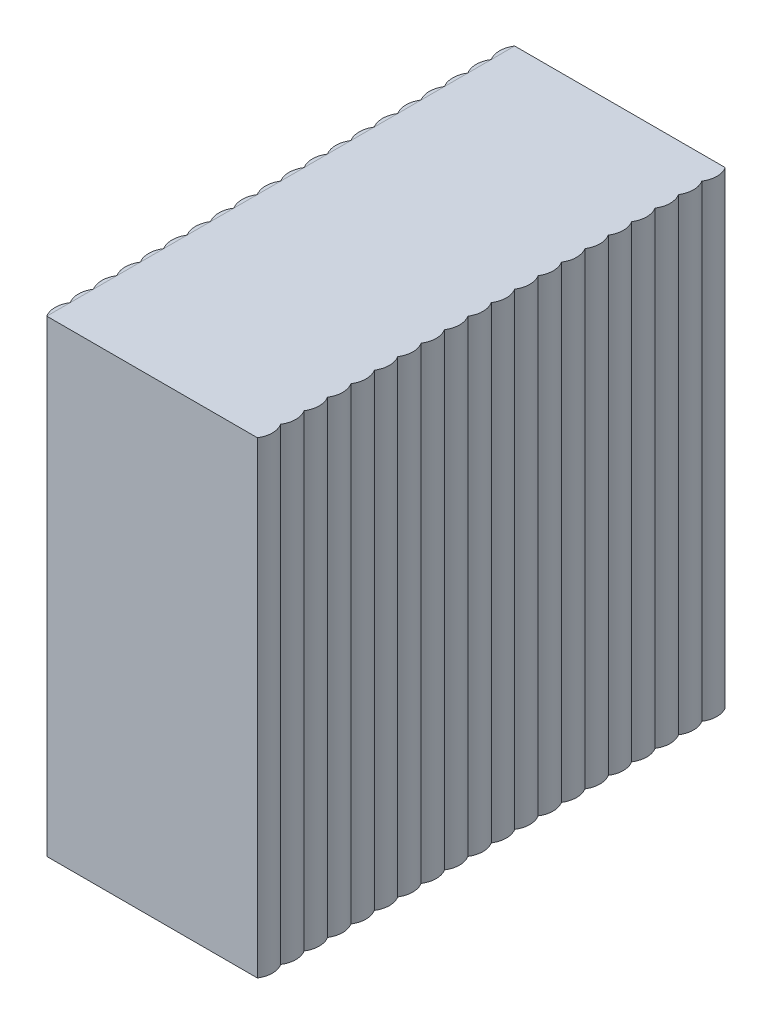
SolidWorks part; units mm, degrees
ref_plane "前视基准面" through (0, 0, 0) normal (0, 0, 1) x (1, 0, 0)
ref_plane "上视基准面" through (0, 0, 0) normal (0, 1, 0) x (1, 0, 0)
ref_plane "右视基准面" through (0, 0, 0) normal (1, 0, 0) x (0, 0, -1)
sketch "草图1" plane through (0, 0, 0) normal (1, 0, 0) x (0, 0, -1)
  line L1 (0, 0) -> (5, 0)
  line L2 (0, 0) -> (0, 5)
  line L3 (0, 5) -> (5, 5)
  line L4 (5, 0) -> (5, 5)
  dimension "D1" = 5
  dimension "D2" = 5
extrude "凸台-拉伸1" add sketch "草图1" along normal blind 2.25
sketch "草图3" plane through (0, 0, 0) normal (0, -1, 0) x (1, 0, 0)
  line L0 (0.1967, -4.875) -> (0.1967, -4.625) construction
  line L2 (-0.0364, -5.0397) -> (-0.0364, -0.0247)
  line L3 (0, -5) -> (0, 0)
  circle A0 centre (0.1967, -4.875) radius 0.2331
  circle A1 centre (0.1967, -4.625) radius 0.2331
  circle A2 centre (0.1967, -4.375) radius 0.2331
  circle A3 centre (0.1967, -4.125) radius 0.2331
  circle A4 centre (0.1967, -3.875) radius 0.2331
  circle A5 centre (0.1967, -3.625) radius 0.2331
  circle A6 centre (0.1967, -3.375) radius 0.2331
  circle A7 centre (0.1967, -3.125) radius 0.2331
  circle A8 centre (0.1967, -2.875) radius 0.2331
  circle A9 centre (0.1967, -2.625) radius 0.2331
  circle A10 centre (0.1967, -2.375) radius 0.2331
  circle A11 centre (0.1967, -2.125) radius 0.2331
  circle A12 centre (0.1967, -1.875) radius 0.2331
  circle A13 centre (0.1967, -1.625) radius 0.2331
  circle A14 centre (0.1967, -1.375) radius 0.2331
  circle A15 centre (0.1967, -1.125) radius 0.2331
  circle A16 centre (0.1967, -0.875) radius 0.2331
  circle A17 centre (0.1967, -0.625) radius 0.2331
  circle A18 centre (0.1967, -0.375) radius 0.2331
  circle A19 centre (0.1967, -0.125) radius 0.2331
  line M21 (0, 0) -> (0, -5)
  dimension "D1" = 20
  dimension "D2" = 0.25
extrude "凸台-拉伸3" add sketch "草图3" against normal up to surface (5 mm away) separate body contours L3 A0 | L3 A1 | L3 A2 | L3 A3 | L3 A4 | L3 A5 | L3 A6 | L3 A7 | L3 A8 | L3 A9 | L3 A10 | L3 A11 | L3 A12 | L3 A13 | L3 A14 | L3 A15 | L3 A16 | L3 A17 | L3 A18 | A19 M21 region at (-0.0146, 0, -4.875) region at (-0.0146, 0, -4.625) region at (-0.0146, 0, -4.375) region at (-0.0146, 0, -4.125) region at (-0.0146, 0, -3.875) region at (-0.0146, 0, -3.625) region at (-0.0146, 0, -3.375) region at (-0.0146, 0, -3.125) region at (-0.0146, 0, -2.875) region at (-0.0146, 0, -2.625) region at (-0.0146, 0, -2.375) region at (-0.0146, 0, -2.125) region at (-0.0146, 0, -1.875) region at (-0.0146, 0, -1.625) region at (-0.0146, 0, -1.375) region at (-0.0146, 0, -1.125) region at (-0.0146, 0, -0.875) region at (-0.0146, 0, -0.625) region at (-0.0146, 0, -0.375) region at (-0.0146, 0, -0.125) up to face at (1.125, 5, -2.5)
ref_plane "基准面1" through (1.125, 0, 0) normal (1, 0, 0) x (0, 0, -1)
mirror "镜向1" about plane through (1.125, 0, 0) normal (1, 0, 0) of "凸台-拉伸3"
